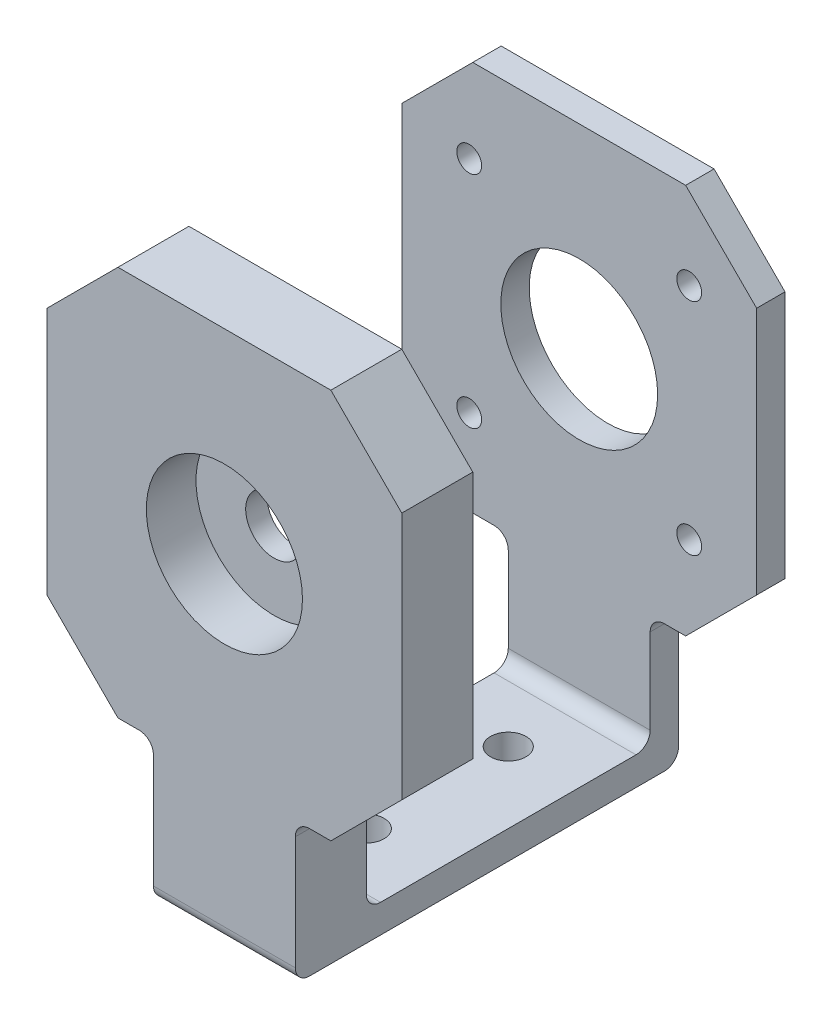
SolidWorks part; units mm, degrees
material "PLA"
ref_plane "Piano frontale" through (0, 0, 0) normal (0, 0, 1) x (1, 0, 0)
ref_plane "Piano superiore" through (0, 0, 0) normal (0, 1, 0) x (1, 0, 0)
ref_plane "Piano destro" through (0, 0, 0) normal (1, 0, 0) x (0, 0, -1)
sketch "Schizzo1" plane through (0, 0, 0) normal (0, 0, 1) x (1, 0, 0)
  line L5 (0, 0) -> (0, -67.5867) construction
  line L6 (-25, -27.5) -> (-10, -27.5)
  line L10 (-25, -27.5) -> (-25, 27.5)
  line L11 (-15.5, 15.5) -> (15.5, 15.5) construction
  line L12 (-15.5, 15.5) -> (-15.5, -15.5) construction
  line L13 (-15.5, -15.5) -> (15.5, -15.5) construction
  line L14 (15.5, 15.5) -> (15.5, -15.5) construction
  line L15 (-15.5, 15.5) -> (15.5, -15.5) construction
  line L16 (-15.5, -15.5) -> (15.5, 15.5) construction
  line L17 (-25, 27.5) -> (25, 27.5)
  line L18 (25, -27.5) -> (25, 27.5)
  line L22 (-25, -27.5) -> (25, 27.5) construction
  line L27 (-25, 27.5) -> (25, -27.5) construction
  line L29 (-10, -47.5) -> (10, -47.5)
  line L31 (-10, -47.5) -> (-10, -27.5)
  line L33 (10, -47.5) -> (10, -27.5)
  line L34 (-10, -47.5) -> (10, -27.5) construction
  line L35 (-10, -27.5) -> (10, -47.5) construction
  line L36 (10, -27.5) -> (25, -27.5)
  circle A0 centre (-15.5, 15.5) radius 1.75
  circle A1 centre (15.5, 15.5) radius 1.75
  circle A2 centre (15.5, -15.5) radius 1.75
  circle A3 centre (-15.5, -15.5) radius 1.75
  circle A4 centre (0, 0) radius 11.05
  point P4 (0, -37.5)
  point P14 (0, 0)
  dimension "D10" = 3.5
  dimension "D11" = 22.1
  dimension "D2" = 50
  dimension "D4" = 20
  dimension "D3" = 55
  dimension "D8" = 31
  dimension "D5" = 20
extrude "Estrusione-Estrusione1" add sketch "Schizzo1" along normal blind 4
sketch "Schizzo14" plane through (0, 0, 4) normal (0, 0, 1) x (1, 0, 0)
  line L0 (10, -47.5) -> (10, -27.5) construction
  line L1 (-10, -47.5) -> (10, -47.5)
  line L2 (-10, -47.5) -> (-10, -43.5)
  line L3 (-10, -43.5) -> (10, -43.5)
  line L4 (10, -47.5) -> (10, -43.5)
  dimension "D1" = 4
extrude "Estrusione-Estrusione2" add sketch "Schizzo14" along normal blind 40
sketch "Schizzo18" plane through (0, 0, 44) normal (0, 0, 1) x (1, 0, 0)
  line L0 (0, 0) -> (0, -60.5983) construction
  line L1 (-25, -27.5) -> (-10, -27.5)
  line L2 (-25, -27.5) -> (-25, 27.5)
  line L9 (-25, 27.5) -> (25, 27.5)
  line L10 (25, -27.5) -> (25, 27.5)
  line L11 (-25, -27.5) -> (25, 27.5) construction
  line L12 (-25, 27.5) -> (25, -27.5) construction
  line L13 (-10, -47.5) -> (10, -47.5)
  line L14 (-10, -47.5) -> (-10, -27.5)
  line L15 (10, -47.5) -> (10, -27.5)
  line L16 (-10, -47.5) -> (10, -27.5) construction
  line L17 (-10, -27.5) -> (10, -47.5) construction
  line L18 (10, -27.5) -> (25, -27.5)
  point P4 (0, -37.5)
  dimension "D4" = 50
  dimension "D5" = 55
  dimension "D6" = 20
  dimension "D7" = 20
extrude "Estrusione-Estrusione3" add sketch "Schizzo18" along normal blind 10
sketch "Schizzo19" plane through (0, 0, 54) normal (0, 0, 1) x (1, 0, 0)
  circle A0 centre (0, 0) radius 11
  dimension "D1" = 22
extrude "Taglio-Estrusione1" cut sketch "Schizzo19" against normal blind 7
sketch "Schizzo20" plane through (0, 0, 47) normal (0, 0, 1) x (1, 0, 0)
  line L0 (10, -27.5) -> (25, -27.5) construction
  circle A0 centre (0, 0) radius 4
  dimension "D1" = 8
extrude "Taglio-Estrusione2" cut sketch "Schizzo20" against normal blind 7
chamfer "Smusso1" distance 10 angle 45 8 edges at (25, 27.5, 2) (25, -27.5, 2) (-25, -27.5, 2) (-25, 27.5, 2) (25, -27.5, 49) (-25, -27.5, 49) (-25, 27.5, 49) (25, 27.5, 49)
fillet "Raccordo1" radius 2 8 edges at (0, -47.5, 0) (-10, -27.5, 2) (10, -27.5, 2) (0, -43.5, 4) (0, -43.5, 44) (0, -47.5, 54) (-10, -27.5, 49) (10, -27.5, 49)
sketch "Schizzo21" plane through (0, -43.5, 0) normal (0, 1, 0) x (1, 0, 0)
  line L0 (0, 0) -> (0, -54) construction
  line L1 (15, -54) -> (-15, -54) construction
  line L2 (-10, -24) -> (10, -24) construction
  line L3 (-10, -42) -> (-10, -6) construction
  line L4 (10, -42) -> (10, -6) construction
  line L5 (-10, -4) -> (10, -4) construction
  circle A0 centre (0, -14) radius 2.5
  circle A1 centre (0, -34) radius 2.5
  dimension "D1" = 10
  dimension "D2" = 5
extrude "Taglio-Estrusione3" cut sketch "Schizzo21" against normal blind 10
